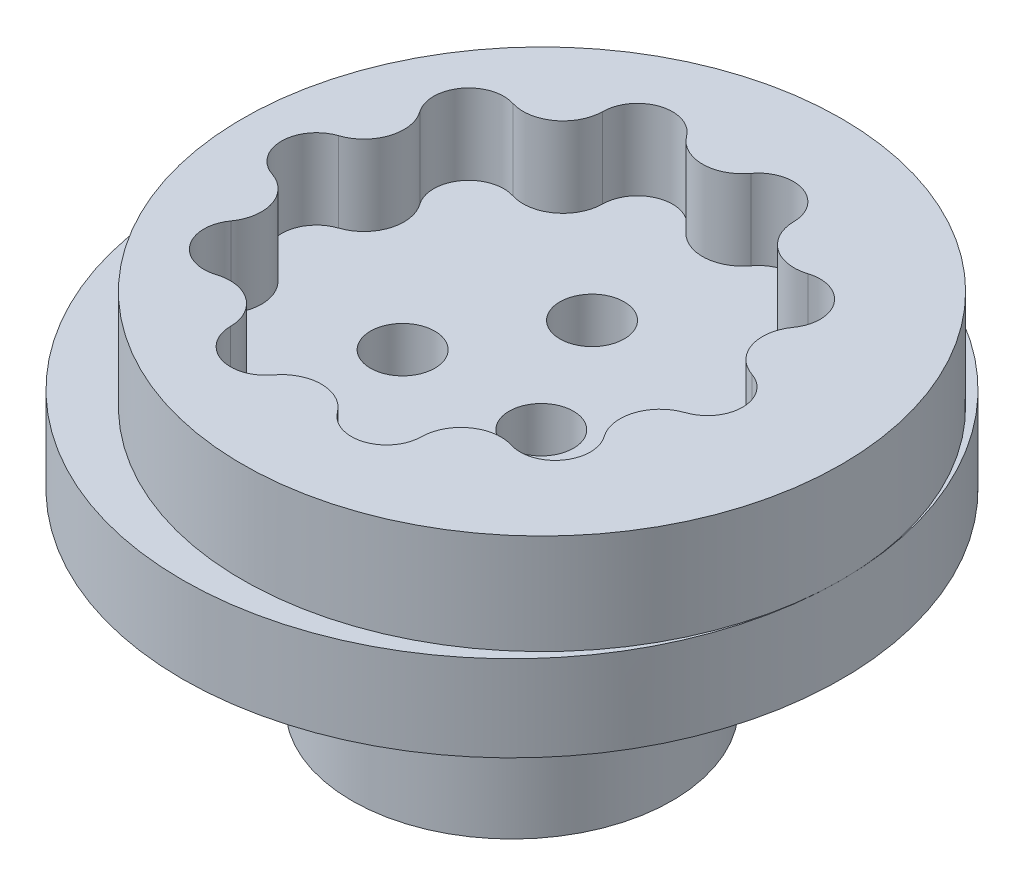
SolidWorks part; units mm, degrees
material "6061 Alloy"
ref_plane "Front" through (0, 0, 0) normal (0, 0, 1) x (1, 0, 0)
ref_plane "Top" through (0, 0, 0) normal (0, 1, 0) x (1, 0, 0)
ref_plane "Right" through (0, 0, 0) normal (1, 0, 0) x (0, 0, -1)
sketch "Sketch1" plane through (0, 0, 0) normal (0, 1, 0) x (1, 0, 0)
  circle A0 centre (0, 0) radius 26.1937 construction
  circle A1 centre (0, 0) radius 26.143
  dimension "D1" = 52.3875
  dimension "D2" = 0.0508
extrude "Boss-Extrude1" add sketch "Sketch1" against normal blind 8.3979
sketch "Sketch2" plane through (0, -8.3979, 0) normal (0, -1, 0) x (1, 0, 0)
  circle A0 centre (0, 0) radius 12.7
  dimension "D1" = 25.4
extrude "Boss-Extrude2" add sketch "Sketch2" along normal blind 15.0812
sketch "Sketch3" plane through (0, 0, 0) normal (0, 1, 0) x (1, 0, 0)
  line L0 (0, 0) -> (0, 26.143) construction
  line L1 (0, 0) -> (15.3664, 21.1501) construction
  arc A0 (2.553, 16.4005) -> (7.5745, 14.7689) centre (4.7912, 14.7457) cw
  circle A2 centre (0, 0) radius 18.288 construction
  arc A3 (0, 15.113) -> (2.553, 16.4005) centre (0, 18.288) ccw
  arc A4 (8.8832, 12.2267) -> (7.5745, 14.7689) centre (10.7494, 14.7953) cw
  arc A5 (8.8832, 12.2267) -> (11.7054, 11.7676) centre (10.7494, 14.7953) ccw
  arc A6 (11.7054, 11.7676) -> (14.8088, 7.4961) centre (12.5434, 9.1133) cw
  arc A7 (14.3733, 4.6702) -> (14.8088, 7.4961) centre (17.3929, 5.6513) cw
  arc A8 (14.3733, 4.6702) -> (16.3867, 2.64) centre (17.3929, 5.6513) ccw
  arc A9 (16.3867, 2.64) -> (16.3867, -2.64) centre (15.5045, 0) cw
  arc A10 (14.3733, -4.6702) -> (16.3867, -2.64) centre (17.3929, -5.6513) cw
  arc A11 (14.3733, -4.6702) -> (14.8088, -7.4961) centre (17.3929, -5.6513) ccw
  arc A12 (14.8088, -7.4961) -> (11.7054, -11.7676) centre (12.5434, -9.1133) cw
  arc A13 (8.8832, -12.2267) -> (11.7054, -11.7676) centre (10.7494, -14.7953) cw
  arc A14 (8.8832, -12.2267) -> (7.5745, -14.7689) centre (10.7494, -14.7953) ccw
  arc A15 (7.5745, -14.7689) -> (2.553, -16.4005) centre (4.7912, -14.7457) cw
  arc A16 (0, -15.113) -> (2.553, -16.4005) centre (0, -18.288) cw
  arc A17 (0, -15.113) -> (-2.553, -16.4005) centre (0, -18.288) ccw
  arc A18 (-2.553, -16.4005) -> (-7.5745, -14.7689) centre (-4.7912, -14.7457) cw
  arc A19 (-8.8832, -12.2267) -> (-7.5745, -14.7689) centre (-10.7494, -14.7953) cw
  arc A20 (-8.8832, -12.2267) -> (-11.7054, -11.7676) centre (-10.7494, -14.7953) ccw
  arc A21 (-11.7054, -11.7676) -> (-14.8088, -7.4961) centre (-12.5434, -9.1133) cw
  arc A22 (-14.3733, -4.6702) -> (-14.8088, -7.4961) centre (-17.3929, -5.6513) cw
  arc A23 (-14.3733, -4.6702) -> (-16.3867, -2.64) centre (-17.3929, -5.6513) ccw
  arc A24 (-16.3867, -2.64) -> (-16.3867, 2.64) centre (-15.5045, 0) cw
  arc A25 (-14.3733, 4.6702) -> (-16.3867, 2.64) centre (-17.3929, 5.6513) cw
  arc A26 (-14.3733, 4.6702) -> (-14.8088, 7.4961) centre (-17.3929, 5.6513) ccw
  arc A27 (-14.8088, 7.4961) -> (-11.7054, 11.7676) centre (-12.5434, 9.1133) cw
  arc A28 (-8.8832, 12.2267) -> (-11.7054, 11.7676) centre (-10.7494, 14.7953) cw
  arc A29 (-8.8832, 12.2267) -> (-7.5745, 14.7689) centre (-10.7494, 14.7953) ccw
  arc A30 (-7.5745, 14.7689) -> (-2.553, 16.4005) centre (-4.7912, 14.7457) cw
  arc A31 (0, 15.113) -> (-2.553, 16.4005) centre (0, 18.288) cw
  circle A32 centre (0, 0) radius 26.143
  circle A33 centre (0, 0) radius 26.143 construction
  point P78 (0, 0)
  dimension "D1" = 36.576
  dimension "D2" = 3.175
  dimension "D3" = 36
extrude "Boss-Extrude3" add sketch "Sketch3" along normal blind 6.35
hole_wizard "1/4-20 Tapped Hole1" positions "Sketch5" profile "Sketch4" tap size "1/4-20" standard "ANSI Inch" end condition through all
sketch "Sketch5" plane through (0, -23.4791, 0) normal (0, -1, 0) x (-1, 0, 0)
  circle A1 centre (0, 0) radius 6.35
  circle A3 centre (0, 0) radius 12.7 construction
  point P2 (0, 6.35)
  point P23 (5.4993, -3.175)
  point P24 (-5.4993, -3.175)
  dimension "D1" = 12.7
  dimension "D2" = 3
sketch "Sketch4" plane through (0, -23.4791, -6.35) normal (1, 0, 0) x (0, 0, -1)
  line L0 (0, 0) -> (0, 29.8291)
  line L1 (0, 29.8291) -> (2.5527, 29.8291)
  line L2 (2.5527, 29.8291) -> (2.5527, 0)
  line L5 (2.5527, 0) -> (0, 0)
  line L11 (0, -6.35) -> (0, 107.95) construction
  dimension "Thread Major Dia." = 5.1054
  dimension "Thru Tap Drill Depth" = 29.8291
sketch "Sketch6" plane through (0, 6.35, 0) normal (0, 1, 0) x (1, 0, 0)
  line L0 (-26.143, 0) -> (26.143, 0) construction
  line L2 (-33.2518, 33.8083) -> (33.2518, 33.8083)
  line L3 (-33.2518, 33.8083) -> (-33.2518, -33.8083)
  line L4 (-33.2518, -33.8083) -> (33.2518, -33.8083)
  line L5 (33.2518, 33.8083) -> (33.2518, -33.8083)
  line L6 (-33.2518, 33.8083) -> (33.2518, -33.8083) construction
  line L7 (-33.2518, -33.8083) -> (33.2518, 33.8083) construction
  circle A0 centre (0, 0) radius 26.143 construction
  arc A1 (26.143, 0) -> (-21.3805, 0) centre (2.3812, 0) cw
  arc A2 (26.143, 0) -> (-21.3805, 0) centre (2.3812, 0) ccw
  point P7 (0, 0)
  dimension "D1" = 4.7625
extrude "Cut-Extrude2" cut sketch "Sketch6" against normal blind 7.9375
